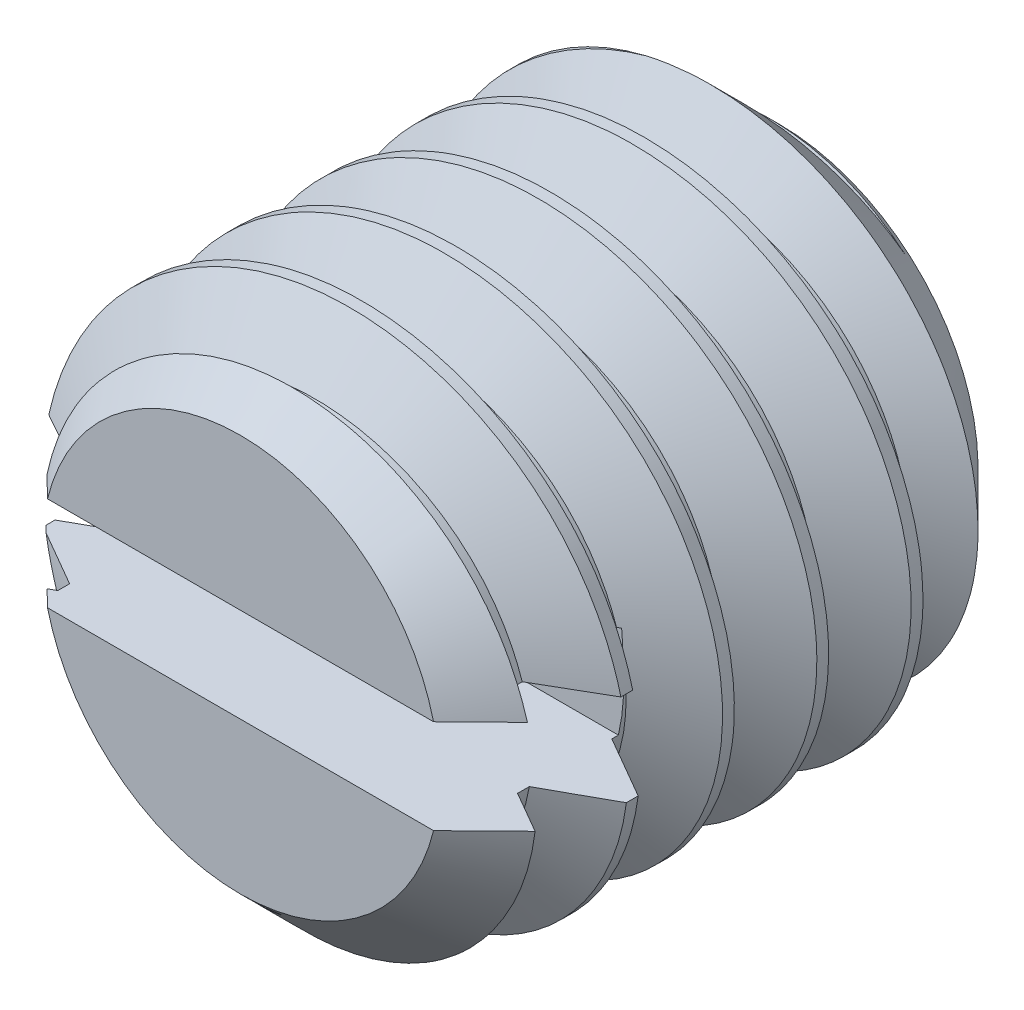
SolidWorks part; units mm, degrees
ref_plane "Front" through (0, 0, 0) normal (0, 0, 1) x (1, 0, 0)
ref_plane "Top" through (0, 0, 0) normal (0, 1, 0) x (1, 0, 0)
ref_plane "Right" through (0, 0, 0) normal (1, 0, 0) x (0, 0, -1)
sketch "Sketch1" plane through (0, 0, 0) normal (1, 0, 0) x (0, 0, -1)
  line L1 (2, 0) -> (-2, 0) construction
  line L3 (-2, 0) -> (-2, 1.475) construction
  line L6 (-2, 1.475) -> (-1.475, 2) construction
  line L8 (-2.6562, 2.0758) -> (-1.9562, 2.0758) construction
  line L10 (-1.9562, 2.0758) -> (-2.3062, 1.4696) construction
  line L11 (-2.3062, 1.4696) -> (-2.6562, 2.0758) construction
  line L12 (-2.3062, 1.4696) -> (-2.3062, 1.5453) construction
  line L13 (-2.35, 1.5453) -> (-2.2625, 1.5453) construction
  line L14 (-2.6125, 2) -> (-2, 2) construction
  line L15 (-2.3062, 2.0758) -> (-2.3062, 2) construction
  line L16 (-2.6344, 2.0379) -> (-1.9781, 2.0379) construction
  line L17 (-1.475, 2) -> (1.475, 2) construction
  line L18 (1.475, 2) -> (2, 1.475) construction
  line L19 (2, 1.475) -> (2, 0) construction
  line L21 (-0.7, -0.35) -> (-2, -0.35)
  line L22 (-0.7, -0.35) -> (-0.7, 0.35)
  line L23 (-0.7, 0.35) -> (-2, 0.35)
  line L24 (-2, -0.35) -> (-2, 0.35)
  line L25 (-1.35, 0.35) -> (-1.35, -0.35) construction
  line L26 (-0.7, 0) -> (-2, 0) construction
  point P0 (-1.35, 0)
  point P3 (0, 0)
  point P22 (-2.3062, 1.5453)
  point P25 (-2.3062, 2)
  point P28 (-2.3062, 2.0379)
  point P32 (1.15, 2)
  point P36 (1.15, -2)
  dimension "Thread Pitch" = 0.7
  dimension "D5" = 0.0875
  dimension "Length" = 4
  dimension "D1" = 45
  dimension "Thread Size" = 4
  dimension "D2" = 0.525
  dimension "Slot Height" = 0.7
  dimension "Slot Depth" = 1.3
  dimension "D3" = 3.15
sketch "Sketch2" plane through (0, 0, 0) normal (1, 0, 0) x (0, 0, -1)
  line L0 (-2, 0) -> (-2, 1.475)
  line L1 (-2, 1.475) -> (-1.475, 2)
  line L2 (-1.475, 2) -> (1.475, 2)
  line L3 (1.475, 2) -> (2, 1.475)
  line L4 (2, 1.475) -> (2, 0)
  line L5 (2, 0) -> (-2, 0)
revolve "Revolve1" add sketch "Sketch2" angle 360 about L5
sketch "Sketch3" plane through (0, 0, 0) normal (1, 0, 0) x (0, 0, -1)
  line L1 (-2, 0.35) -> (-0.7, 0.35)
  line L2 (-2, 0.35) -> (-2, -0.35)
  line L3 (-2, -0.35) -> (-0.7, -0.35)
  line L4 (-0.7, 0.35) -> (-0.7, -0.35)
extrude "Cut-Extrude1" cut sketch "Sketch3" against normal through all both and the other way through all
sketch "Sketch4" plane through (0, 0, 2) normal (0, 0, 1) x (1, 0, 0)
  line L0 (0, 0.35) -> (0, -0.35) construction
  circle A0 centre (0, 0) radius 2
ref_axis "Center Axis 1" through (0, 0, 1.475) along (0, 0, -1)
curve "Helix/Spiral1" pitch 0.7 height 4.7 radius 2 centre (0, 0, 2) axis (0, 0, -1) start towards (0, 1, 0)
sketch "Sketch5" plane through (0, 0, 0) normal (1, 0, 0) x (0, 0, -1)
  line L0 (-2.6344, 2.0379) -> (-1.9781, 2.0379)
  line L1 (-1.9781, 2.0379) -> (-2.2625, 1.5453)
  line L2 (-1.9562, 2.0758) -> (-2.3062, 1.4696) construction
  line L3 (-2.2625, 1.5453) -> (-2.35, 1.5453)
  line L4 (-2.35, 1.5453) -> (-2.6344, 2.0379)
sweep "Cut-Sweep1" cut profiles "Sketch5" path "Helix/Spiral1"
equation "\"D2@Sketch1\"=\"Thread Pitch@Sketch1\"*.75"
equation "\"D3@Helix/Spiral1\"=\"Length@Sketch1\"+\"D4@Helix/Spiral1\""
equation "\"D4@Helix/Spiral1\"=\"Thread Pitch@Sketch1\""
equation "\"D5@Sketch1\"=\"Thread Pitch@Sketch1\"/8"
equation "\"D3@Sketch1\"=\"Thread Pitch@Sketch1\"*4.5"
